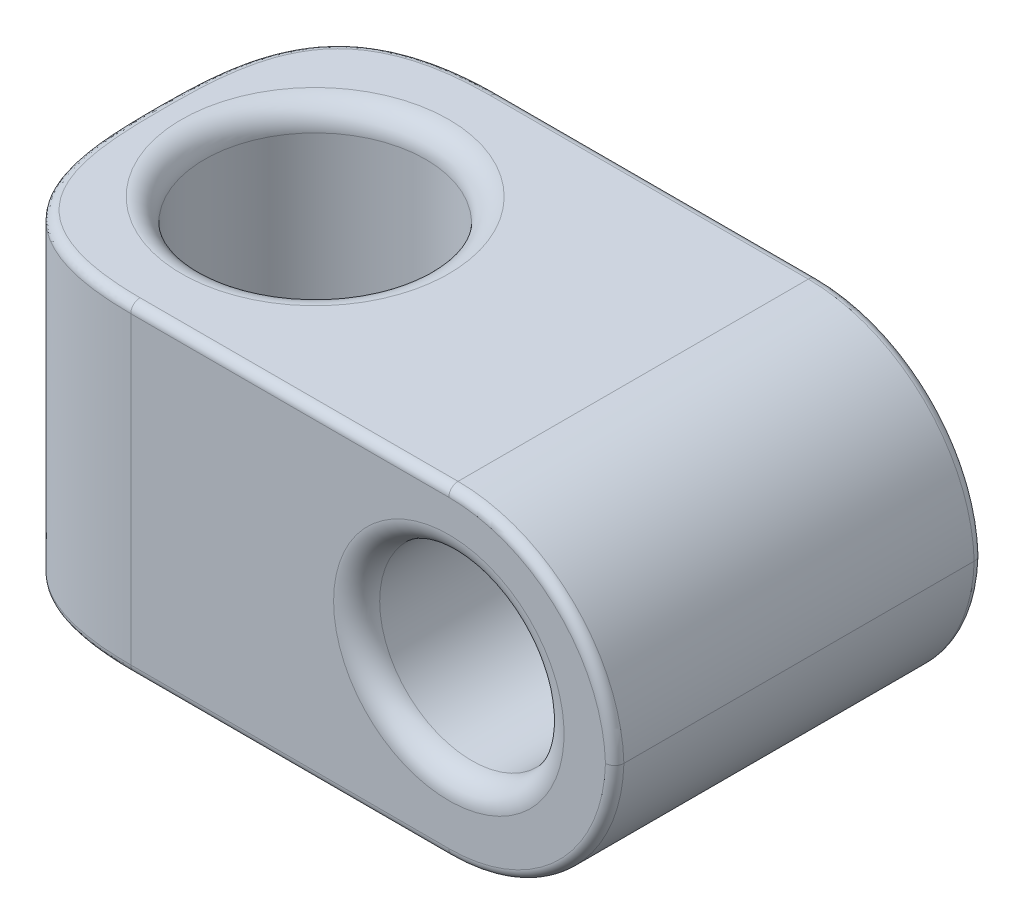
SolidWorks part; units mm, degrees
ref_plane "Front Plane" through (0, 0, 0) normal (0, 0, 1) x (1, 0, 0)
ref_plane "Top Plane" through (0, 0, 0) normal (0, 1, 0) x (1, 0, 0)
ref_plane "Right Plane" through (0, 0, 0) normal (1, 0, 0) x (0, 0, -1)
sketch "Sketch1" plane through (0, 0, 0) normal (0, 1, 0) x (1, 0, 0)
  line L0 (0, 0) -> (-35, 0) construction
  line L1 (-17.5, -20) -> (35, -20)
  line L3 (-17.5, 20) -> (35, 20)
  line L4 (35, -20) -> (35, 20)
  line L5 (-25.6218, -14.641) -> (35, 20) construction
  line L6 (-35, 20) -> (35, -20) construction
  line L7 (-17.5, 0) -> (-17.5, 20) construction
  line L8 (-17.5, 0) -> (-17.5, -20) construction
  circle A0 centre (-17.5, 0) radius 12
  spline S0 degree 3 poles (-17.5, 20) (-34.1667, 20) (-35.8333, 0) (-34.1667, -20) (-17.5, -20) knots 0 0 0 0 0.5 1 1 1 1
  point P0 (0, 0)
  dimension "D3" = 24
  dimension "D1" = 50
  dimension "D2" = 50
extrude "Boss-Extrude1" add sketch "Sketch1" along normal blind 35
fillet "Fillet1" radius 18 2 edges at (35, 0, 0) (35, 35, 0)
sketch "Sketch2" plane through (0, 0, -20) normal (0, 0, -1) x (-1, 0, 0)
  circle A0 centre (-17, 18) radius 10
  dimension "D1" = 20
extrude "Cut-Extrude1" cut sketch "Sketch2" against normal through all
fillet "Fillet2" radius 2.5 4 edges at (-17.5, 35, 12) (-17.5, 0, 12) (7, 18, 20) (7, 18, -20)
fillet "Fillet3" radius 1 10 edges at (29.5499, 29.9035, -20) (29.5499, 29.9035, 20) (-0.25, 35, 20) (29.5499, 5.0965, 20) (-0.25, 0, 20) (-0.25, 0, -20) (-0.25, 35, -20) (29.5499, 5.0965, -20)
